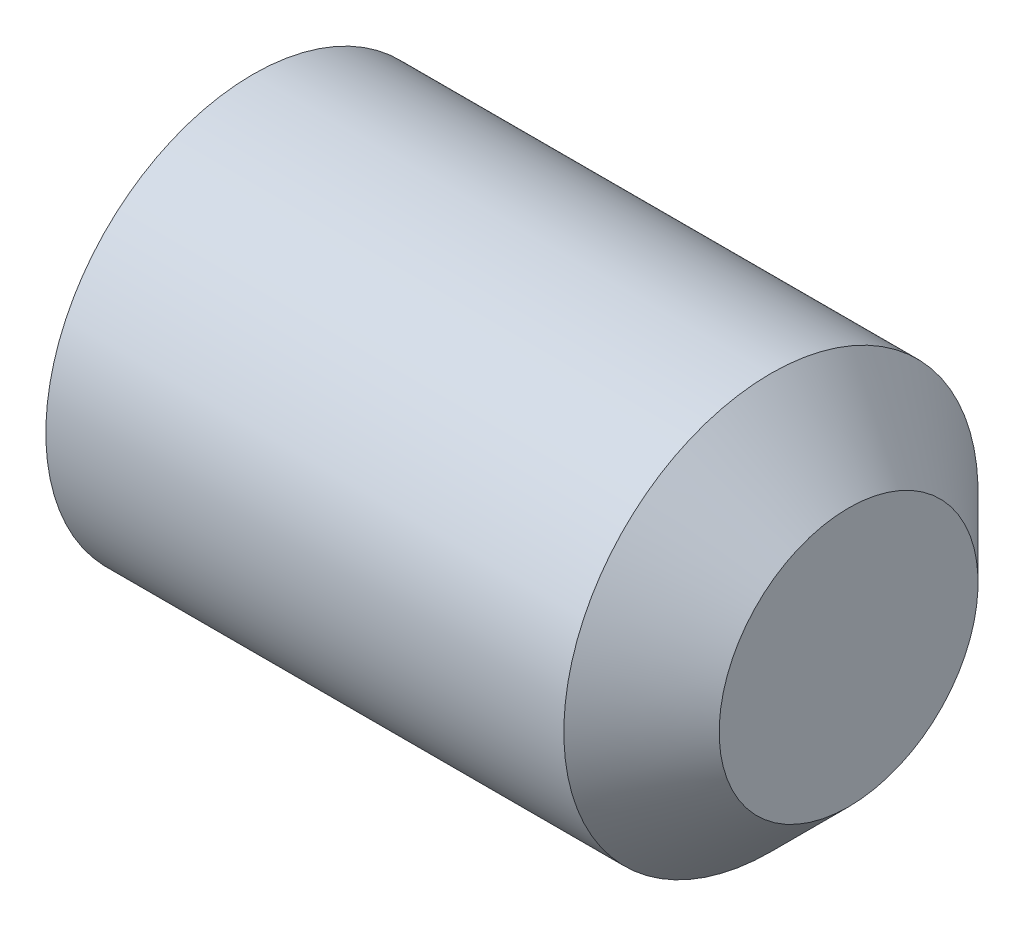
SolidWorks part; units mm, degrees
material "6061 合金"
ref_plane "前视基准面" through (0, 0, 0) normal (0, 0, 1) x (1, 0, 0)
ref_plane "上视基准面" through (0, 0, 0) normal (0, 1, 0) x (1, 0, 0)
ref_plane "右视基准面" through (0, 0, 0) normal (1, 0, 0) x (0, 0, -1)
sketch "草图1" plane through (0, 0, 0) normal (0, 0, 1) x (1, 0, 0)
  line L0 (6, 0) -> (6, -1.25)
  line L1 (6, -1.25) -> (5.25, -2)
  line L2 (5.25, -2) -> (0.248, -2)
  line L3 (0.248, -2) -> (0, -1.5705)
  line L4 (0, -1.5705) -> (0, -1.1547)
  line L5 (0, -1.1547) -> (0.6667, 0)
  line L6 (0.6667, 0) -> (6, 0)
  line L7 (0.6667, 0) -> (6, 0) construction
revolve "旋转1" add sketch "草图1" angle 360 about L7
cosmetic thread "装饰螺纹线1" parameters "D1"=5.6795, "D2"=3.141
sketch "草图2" plane through (0, 0, 0) normal (1, 0, 0) x (0, 0, -1)
  line L0 (-1.1547, 0) -> (-0.5774, -1)
  line L1 (-0.5774, -1) -> (0.5774, -1)
  line L2 (0.5774, -1) -> (1.1547, 0)
  line L3 (1.1547, 0) -> (0.5774, 1)
  line L4 (0.5774, 1) -> (-0.5774, 1)
  line L5 (-0.5774, 1) -> (-1.1547, 0)
extrude "切除-拉伸1" cut sketch "草图2" along normal blind 2.5
ref_plane "基准面1" through (6, 0, 0) normal (1, 0, 0) x (0, 0, -1)
ref_plane "IP1 XY" through (0, 0, 0) normal (1, 0, 0) x (0, 0, -1)
ref_plane "IP1 XZ" through (0, 0, 0) normal (0, -1, 0) x (-1, 0, 0)
ref_plane "IP1 YZ" through (0, 0, 0) normal (0, 0, -1) x (-1, 0, 0)
ref_axis "IP1 X" through (0, 0, 80.9) along (0, 0, -1)
ref_axis "IP1 Y" through (0, -50, 0) along (0, 1, 0)
ref_axis "IP1 Z" through (80.9, 0, 0) along (-1, 0, 0)
sketch3d "IP1"
  point P0 (0, 0, 0)
ref_plane "IP2 XY" through (6, 0, 0) normal (1, 0, 0) x (0, 0, -1)
ref_plane "IP2 XZ" through (0, 0, 0) normal (0, -1, 0) x (-1, 0, 0)
ref_plane "IP2 YZ" through (0, 0, 0) normal (0, 0, -1) x (-1, 0, 0)
ref_axis "IP2 X" through (6, 0, 80.9) along (0, 0, -1)
ref_axis "IP2 Y" through (6, -50, 0) along (0, 1, 0)
ref_axis "IP2 Z" through (80.9, 0, 0) along (-1, 0, 0)
sketch3d "IP2"
  point P0 (6, 0, 0)
